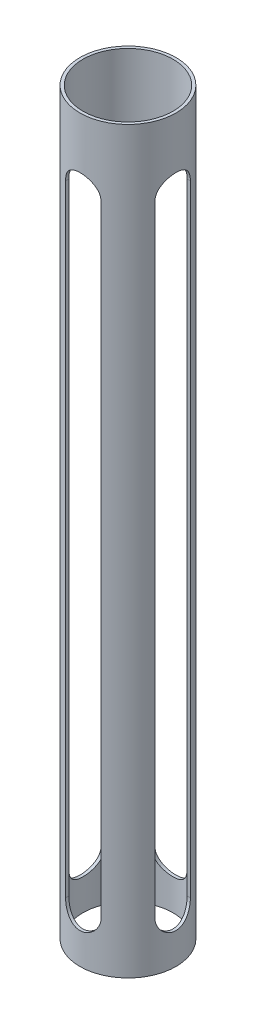
SolidWorks part; units mm, degrees
material "7075-T6 (SN)"
ref_plane "Front Plane" through (0, 0, 0) normal (0, 0, 1) x (1, 0, 0)
ref_plane "Top Plane" through (0, 0, 0) normal (0, 1, 0) x (1, 0, 0)
ref_plane "Right Plane" through (0, 0, 0) normal (1, 0, 0) x (0, 0, -1)
sketch "Sketch1" plane through (0, 0, 0) normal (0, 1, 0) x (1, 0, 0)
  circle A0 centre (0, 0) radius 32.5
  circle A1 centre (0, 0) radius 30.5
extrude "Boss-Extrude1" add sketch "Sketch1" along normal blind 500
sketch "Sketch2" plane through (0, 0, 0) normal (0, 0, 1) x (1, 0, 0)
  line L0 (0, 480) -> (0, 428.756) construction
  line L2 (0, 453.0807) -> (0, 33.0807) construction
  line L3 (12, 453.0807) -> (12, 33.0807)
  line L4 (-12, 453.0807) -> (-12, 33.0807)
  arc A0 (12, 453.0807) -> (-12, 453.0807) centre (0, 453.0807) ccw
  arc A1 (-12, 33.0807) -> (12, 33.0807) centre (0, 33.0807) ccw
  point P3 (0, 243.0807)
extrude "Cut-Extrude1" cut sketch "Sketch2" against normal mid plane 100
sketch "Sketch5" plane through (0, 0, 0) normal (1, 0, 0) x (0, 0, -1)
  line L0 (0, 453.0807) -> (0, 33.0807) construction
  line L1 (12, 453.0807) -> (12, 33.0807)
  line L2 (-12, 453.0807) -> (-12, 33.0807)
  arc A0 (12, 453.0807) -> (-12, 453.0807) centre (0, 453.0807) ccw
  arc A1 (-12, 33.0807) -> (12, 33.0807) centre (0, 33.0807) ccw
  point P3 (0, 243.0807)
extrude "Cut-Extrude3" cut sketch "Sketch5" against normal mid plane 100
